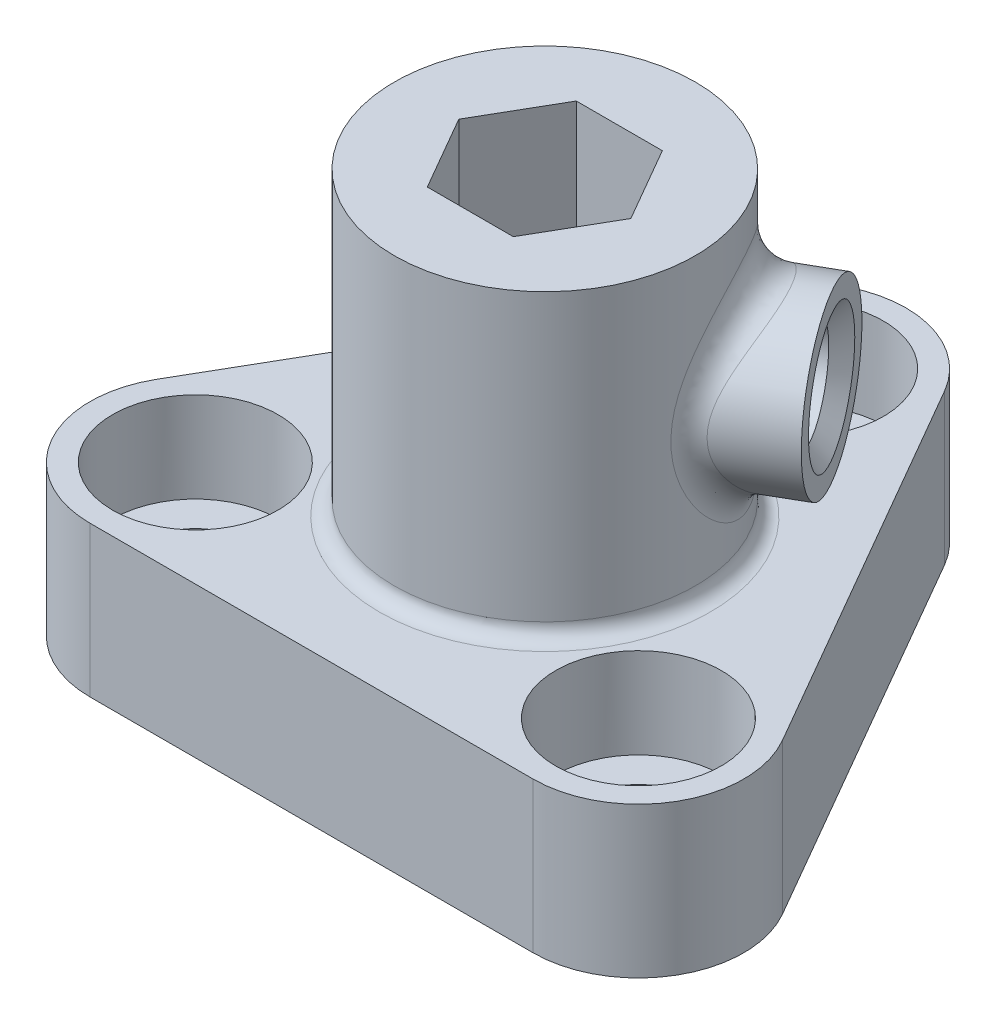
SolidWorks part; units mm, degrees
ref_plane "Front Plane" through (0, 0, 0) normal (0, 0, 1) x (1, 0, 0)
ref_plane "Top Plane" through (0, 0, 0) normal (0, 1, 0) x (1, 0, 0)
ref_plane "Right Plane" through (0, 0, 0) normal (1, 0, 0) x (0, 0, -1)
sketch "Sketch1" plane through (0, 0, 0) normal (1, 0, 0) x (0, 0, -1)
  line L1 (0, 0) -> (12, 0)
  line L2 (0, 0) -> (0, 5.3535)
  line L3 (5, 5) -> (12, 5)
  line L4 (12, 0) -> (12, 5)
  line L6 (0, 5.3535) -> (0, 15)
  line L7 (0, 15) -> (5, 15)
  line L8 (5, 5) -> (5, 15)
  dimension "D1" = 15
  dimension "6" = 5
  dimension "D3" = 5
  dimension "D4" = 7
revolve "Revolve1" add sketch "Sketch1" angle 360 about L6
sketch "Sketch4" plane through (0, 5, 0) normal (0, 1, 0) x (1, 0, 0)
  circle A0 centre (0, 8.5) radius 2.75
  circle A1 centre (7.3612, -4.25) radius 2.75
  circle A2 centre (-7.3612, -4.25) radius 2.75
  circle A6 centre (0, 0) radius 8.5 construction
  point P15 (0, 0)
  dimension "D2" = 17
  dimension "D3" = 5.5
  dimension "D1" = 3
extrude "Cut-Extrude4" cut sketch "Sketch4" against normal offset from surface (3 mm away) 2 up to face at (0, 0, -12)
sketch "Sketch5" plane through (0, 5, 0) normal (0, 1, 0) x (1, 0, 0)
  line L0 (-3.0311, 10.25) -> (-10.3923, -2.5)
  line L1 (-7.3612, -7.75) -> (7.3612, -7.75)
  line L2 (3.0311, 10.25) -> (10.3923, -2.5)
  arc A0 (3.0311, 10.25) -> (-3.0311, 10.25) centre (0, 8.5) ccw
  arc A1 (7.3612, -7.75) -> (10.3923, -2.5) centre (7.3612, -4.25) ccw
  arc A2 (-10.3923, -2.5) -> (-7.3612, -7.75) centre (-7.3612, -4.25) ccw
  circle A3 centre (0, 0) radius 12 construction
extrude "Cut-Extrude5" cut sketch "Sketch5" against normal through all flip side to cut
sketch "Sketch2" plane through (0, 15, 0) normal (0, 1, 0) x (1, 0, 0)
  line L0 (10.3923, -2.5) -> (3.0311, 10.25) construction
  line L1 (2.8579, 0) -> (1.4289, 2.475)
  line L2 (1.4289, 2.475) -> (-1.4289, 2.475)
  line L3 (-1.4289, 2.475) -> (-2.8579, 0)
  line L4 (-2.8579, 0) -> (-1.4289, -2.475)
  line L5 (-1.4289, -2.475) -> (1.4289, -2.475)
  line L6 (1.4289, -2.475) -> (2.8579, 0)
  circle A0 centre (0, 0) radius 2.475 construction
  dimension "D1" = 4.95
extrude "Cut-Extrude2" cut sketch "Sketch2" against normal up to surface (10 mm away) up to face at (0, 5, -5.75)
ref_plane "Plane1" through (6.0405, 0, -3.4875) normal (-0.866, 0, 0.5) x (0.5, 0, 0.866)
sketch "Sketch3" plane through (6.0405, 0, -3.4875) normal (0.866, 0, -0.5) x (-0.5, 0, -0.866)
  line L0 (0, 15) -> (0, 5) construction
  line L1 (1.4289, 15) -> (-1.4289, 15) construction
  line L3 (5, 5) -> (-5, 5) construction
  circle A0 centre (0, 10) radius 2.75
  point P10 (0, 10)
  dimension "D1" = 5.5
extrude "Boss-Extrude1" add sketch "Sketch3" against normal up to next
sketch "Sketch6" plane through (6.0405, 0, -3.4875) normal (0.866, 0, -0.5) x (-0.5, 0, -0.866)
  circle A0 centre (0, 10) radius 1.6
  dimension "D1" = 3.2
extrude "Cut-Extrude6" cut sketch "Sketch6" against normal up to next
fillet "Fillet1" radius 0.5 1 edges at (0, 5, -5)
chamfer "Chamfer1" distance 0.5 angle 45 1 edges at (5.2405, 10, -4.8731)
fillet "Fillet2" radius 1 1 edges at (4.9921, 9.766, 0.2817)
sketch "Sketch7" plane through (0, 5, 0) normal (0, 1, 0) x (1, 0, 0)
  circle A0 centre (0, 8.5) radius 1.55
  circle A1 centre (7.3612, -4.25) radius 1.55
  circle A2 centre (-7.3612, -4.25) radius 1.55
  dimension "D1" = 3.1
extrude "Cut-Extrude7" cut sketch "Sketch7" against normal through all
